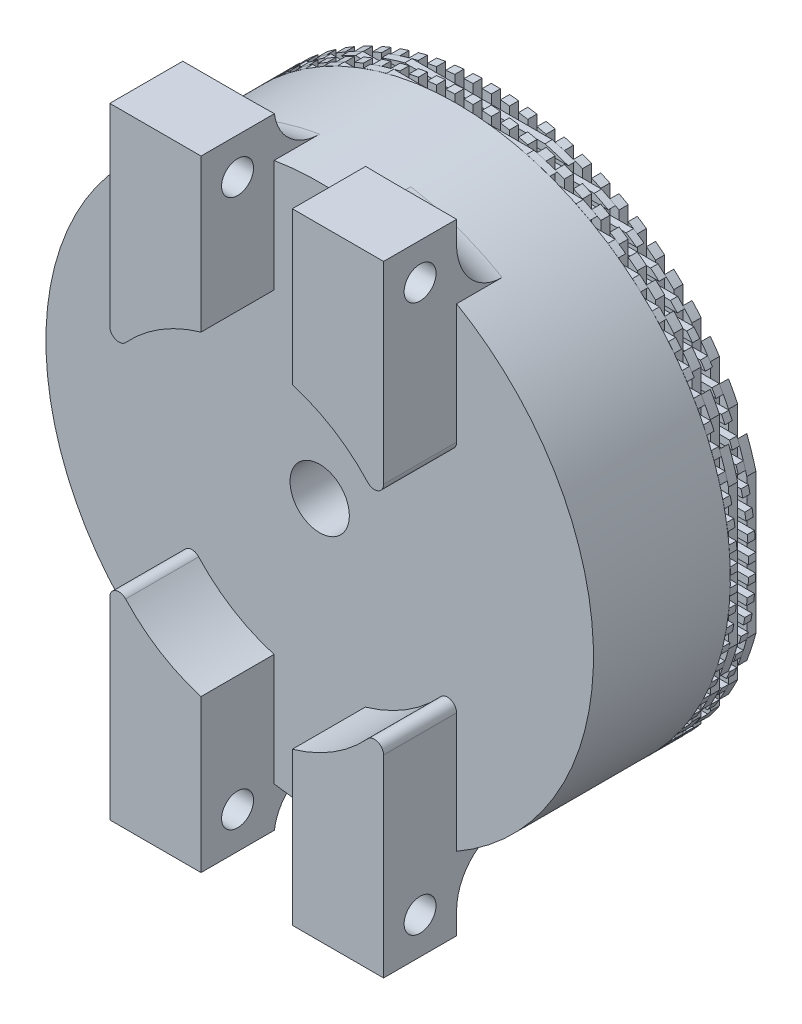
SolidWorks part; units mm, degrees
ref_plane "Front Plane" through (0, 0, 0) normal (1, 0, 0) x (0, 1, 0)
ref_plane "Top Plane" through (0, 0, 0) normal (0, 0, 1) x (0, 1, 0)
ref_plane "Right Plane" through (0, 0, 0) normal (0, 1, 0) x (-1, 0, 0)
sketch "Sketch1" plane through (0, 0, 0) normal (1, 0, 0) x (0, 1, 0)
  line L0 (64, -4) -> (68, -4) construction
  line L1 (0, 0) -> (68, 0)
  line L2 (0, 0) -> (0, -8)
  line L3 (0, -8) -> (68, -8)
  line L4 (68, 0) -> (68, -8)
  line L5 (4, -4) -> (0, -4) construction
  circle A0 centre (4, -4) radius 1.75
  circle A1 centre (64, -4) radius 1.75
  point P10 (0, -4)
  dimension "D1" = 3.5
  dimension "D2" = 60
  dimension "D3" = 8
  dimension "D4" = 4
extrude "Boss-Extrude1" add sketch "Sketch1" along normal blind 30
sketch "Sketch3" plane through (0, 0, -8) normal (0, 0, -1) x (1, 0, 0)
  line L1 (30, 0) -> (30, -68) construction
  line L2 (15, -34) -> (30, -34) construction
  line L3 (15, -34) -> (0, -34) construction
  line L4 (0, 0) -> (0, -68) construction
  circle A0 centre (15, -34) radius 30
  dimension "D1" = 60
extrude "Boss-Extrude2" add sketch "Sketch3" along normal blind 15
sketch "Sketch4" plane through (0, 0, 0) normal (0, 0, 1) x (1, 0, 0)
  circle A0 centre (15, 34) radius 18
  dimension "D1" = 36
extrude "Cut-Extrude1" cut sketch "Sketch4" against normal up to surface (8 mm away) and the other way through all up to face at (37.5, 34, -8)
ref_plane "Plane1" through (15, 0, 0) normal (1, 0, 0) x (0, 0, -1)
sketch "Sketch5" plane through (15, 0, 0) normal (1, 0, 0) x (0, 0, -1)
  line L0 (23, 4) -> (23, 64) construction
  line L1 (23, 63) -> (23.8, 63)
  line L2 (23, 63) -> (23, 62.2)
  line L3 (23, 62.2) -> (23.8, 62.2)
  line L4 (23.8, 63) -> (23.8, 62.2)
  line L5 (23, 64) -> (8, 64) construction
  line L6 (23, 61) -> (23, 60.2)
  line L7 (23, 61) -> (23.8, 61)
  line L8 (23.8, 61) -> (23.8, 60.2)
  line L9 (23, 60.2) -> (23.8, 60.2)
  line L10 (23, 59) -> (23, 58.2)
  line L11 (23, 59) -> (23.8, 59)
  line L12 (23.8, 59) -> (23.8, 58.2)
  line L13 (23, 58.2) -> (23.8, 58.2)
  line L14 (23, 57) -> (23, 56.2)
  line L15 (23, 57) -> (23.8, 57)
  line L16 (23.8, 57) -> (23.8, 56.2)
  line L17 (23, 56.2) -> (23.8, 56.2)
  line L18 (23, 55) -> (23, 54.2)
  line L19 (23, 55) -> (23.8, 55)
  line L20 (23.8, 55) -> (23.8, 54.2)
  line L21 (23, 54.2) -> (23.8, 54.2)
  line L22 (23, 53) -> (23, 52.2)
  line L23 (23, 53) -> (23.8, 53)
  line L24 (23.8, 53) -> (23.8, 52.2)
  line L25 (23, 52.2) -> (23.8, 52.2)
  line L26 (23, 51) -> (23, 50.2)
  line L27 (23, 51) -> (23.8, 51)
  line L28 (23.8, 51) -> (23.8, 50.2)
  line L29 (23, 50.2) -> (23.8, 50.2)
  line L30 (23, 49) -> (23, 48.2)
  line L31 (23, 49) -> (23.8, 49)
  line L32 (23.8, 49) -> (23.8, 48.2)
  line L33 (23, 48.2) -> (23.8, 48.2)
  line L34 (23, 47) -> (23, 46.2)
  line L35 (23, 47) -> (23.8, 47)
  line L36 (23.8, 47) -> (23.8, 46.2)
  line L37 (23, 46.2) -> (23.8, 46.2)
  line L38 (23, 45) -> (23, 44.2)
  line L39 (23, 45) -> (23.8, 45)
  line L40 (23.8, 45) -> (23.8, 44.2)
  line L41 (23, 44.2) -> (23.8, 44.2)
  line L42 (23, 43) -> (23, 42.2)
  line L43 (23, 43) -> (23.8, 43)
  line L44 (23.8, 43) -> (23.8, 42.2)
  line L45 (23, 42.2) -> (23.8, 42.2)
  line L46 (23, 41) -> (23, 40.2)
  line L47 (23, 41) -> (23.8, 41)
  line L48 (23.8, 41) -> (23.8, 40.2)
  line L49 (23, 40.2) -> (23.8, 40.2)
  line L50 (23, 39) -> (23, 38.2)
  line L51 (23, 39) -> (23.8, 39)
  line L52 (23.8, 39) -> (23.8, 38.2)
  line L53 (23, 38.2) -> (23.8, 38.2)
  line L54 (23, 37) -> (23, 36.2)
  line L55 (23, 37) -> (23.8, 37)
  line L56 (23.8, 37) -> (23.8, 36.2)
  line L57 (23, 36.2) -> (23.8, 36.2)
  line L58 (23, 35) -> (23, 34.2)
  line L59 (23, 35) -> (23.8, 35)
  line L60 (23.8, 35) -> (23.8, 34.2)
  line L61 (23, 34.2) -> (23.8, 34.2)
  line L62 (23, 33) -> (23, 32.2)
  line L63 (23, 33) -> (23.8, 33)
  line L64 (23.8, 33) -> (23.8, 32.2)
  line L65 (23, 32.2) -> (23.8, 32.2)
  line L66 (23, 31) -> (23, 30.2)
  line L67 (23, 31) -> (23.8, 31)
  line L68 (23.8, 31) -> (23.8, 30.2)
  line L69 (23, 30.2) -> (23.8, 30.2)
  line L70 (23, 29) -> (23, 28.2)
  line L71 (23, 29) -> (23.8, 29)
  line L72 (23.8, 29) -> (23.8, 28.2)
  line L73 (23, 28.2) -> (23.8, 28.2)
  line L74 (23, 27) -> (23, 26.2)
  line L75 (23, 27) -> (23.8, 27)
  line L76 (23.8, 27) -> (23.8, 26.2)
  line L77 (23, 26.2) -> (23.8, 26.2)
  line L78 (23, 25) -> (23, 24.2)
  line L79 (23, 25) -> (23.8, 25)
  line L80 (23.8, 25) -> (23.8, 24.2)
  line L81 (23, 24.2) -> (23.8, 24.2)
  line L82 (23, 23) -> (23, 22.2)
  line L83 (23, 23) -> (23.8, 23)
  line L84 (23.8, 23) -> (23.8, 22.2)
  line L85 (23, 22.2) -> (23.8, 22.2)
  line L86 (23, 21) -> (23, 20.2)
  line L87 (23, 21) -> (23.8, 21)
  line L88 (23.8, 21) -> (23.8, 20.2)
  line L89 (23, 20.2) -> (23.8, 20.2)
  line L90 (23, 19) -> (23, 18.2)
  line L91 (23, 19) -> (23.8, 19)
  line L92 (23.8, 19) -> (23.8, 18.2)
  line L93 (23, 18.2) -> (23.8, 18.2)
  line L94 (23, 17) -> (23, 16.2)
  line L95 (23, 17) -> (23.8, 17)
  line L96 (23.8, 17) -> (23.8, 16.2)
  line L97 (23, 16.2) -> (23.8, 16.2)
  line L98 (23, 15) -> (23, 14.2)
  line L99 (23, 15) -> (23.8, 15)
  line L100 (23.8, 15) -> (23.8, 14.2)
  line L101 (23, 14.2) -> (23.8, 14.2)
  line L102 (23, 13) -> (23, 12.2)
  line L103 (23, 13) -> (23.8, 13)
  line L104 (23.8, 13) -> (23.8, 12.2)
  line L105 (23, 12.2) -> (23.8, 12.2)
  line L106 (23, 11) -> (23, 10.2)
  line L107 (23, 11) -> (23.8, 11)
  line L108 (23.8, 11) -> (23.8, 10.2)
  line L109 (23, 10.2) -> (23.8, 10.2)
  line L110 (23, 9) -> (23, 8.2)
  line L111 (23, 9) -> (23.8, 9)
  line L112 (23.8, 9) -> (23.8, 8.2)
  line L113 (23, 8.2) -> (23.8, 8.2)
  line L114 (23, 7) -> (23, 6.2)
  line L115 (23, 7) -> (23.8, 7)
  line L116 (23.8, 7) -> (23.8, 6.2)
  line L117 (23, 6.2) -> (23.8, 6.2)
  line L118 (23, 5) -> (23, 4.2)
  line L119 (23, 5) -> (23.8, 5)
  line L120 (23.8, 5) -> (23.8, 4.2)
  line L121 (23, 4.2) -> (23.8, 4.2)
  line L122 (23, 3) -> (23, 2.2)
  line L123 (23, 3) -> (23.8, 3)
  line L124 (23.8, 3) -> (23.8, 2.2)
  line L125 (23, 2.2) -> (23.8, 2.2)
  line L126 (23, 63) -> (23, 61) construction
  dimension "D1" = 0.8
  dimension "D2" = 1
  dimension "D4" = 2
  dimension "D3" = 31
extrude "Boss-Extrude3" add sketch "Sketch5" along normal mid plane 75 separate body
ref_plane "Plane2" through (0, 34, 0) normal (0, -1, 0) x (-1, 0, 0)
sketch "Sketch6" plane through (0, 34, 0) normal (0, -1, 0) x (-1, 0, 0)
  line L0 (-52.5, 23.8) -> (22.5, 23.8) construction
  line L1 (-44, 23.8) -> (-43, 23.8)
  line L2 (-44, 23.8) -> (-44, 24.8)
  line L3 (-44, 24.8) -> (-43, 24.8)
  line L4 (-43, 23.8) -> (-43, 24.8)
  line L5 (-45, 23) -> (-45, 8) construction
  line L6 (-42, 23.8) -> (-42, 24.8)
  line L7 (-42, 23.8) -> (-41, 23.8)
  line L8 (-41, 23.8) -> (-41, 24.8)
  line L9 (-42, 24.8) -> (-41, 24.8)
  line L10 (-40, 23.8) -> (-40, 24.8)
  line L11 (-40, 23.8) -> (-39, 23.8)
  line L12 (-39, 23.8) -> (-39, 24.8)
  line L13 (-40, 24.8) -> (-39, 24.8)
  line L14 (-38, 23.8) -> (-38, 24.8)
  line L15 (-38, 23.8) -> (-37, 23.8)
  line L16 (-37, 23.8) -> (-37, 24.8)
  line L17 (-38, 24.8) -> (-37, 24.8)
  line L18 (-36, 23.8) -> (-36, 24.8)
  line L19 (-36, 23.8) -> (-35, 23.8)
  line L20 (-35, 23.8) -> (-35, 24.8)
  line L21 (-36, 24.8) -> (-35, 24.8)
  line L22 (-34, 23.8) -> (-34, 24.8)
  line L23 (-34, 23.8) -> (-33, 23.8)
  line L24 (-33, 23.8) -> (-33, 24.8)
  line L25 (-34, 24.8) -> (-33, 24.8)
  line L26 (-32, 23.8) -> (-32, 24.8)
  line L27 (-32, 23.8) -> (-31, 23.8)
  line L28 (-31, 23.8) -> (-31, 24.8)
  line L29 (-32, 24.8) -> (-31, 24.8)
  line L30 (-30, 23.8) -> (-30, 24.8)
  line L31 (-30, 23.8) -> (-29, 23.8)
  line L32 (-29, 23.8) -> (-29, 24.8)
  line L33 (-30, 24.8) -> (-29, 24.8)
  line L34 (-28, 23.8) -> (-28, 24.8)
  line L35 (-28, 23.8) -> (-27, 23.8)
  line L36 (-27, 23.8) -> (-27, 24.8)
  line L37 (-28, 24.8) -> (-27, 24.8)
  line L38 (-26, 23.8) -> (-26, 24.8)
  line L39 (-26, 23.8) -> (-25, 23.8)
  line L40 (-25, 23.8) -> (-25, 24.8)
  line L41 (-26, 24.8) -> (-25, 24.8)
  line L42 (-24, 23.8) -> (-24, 24.8)
  line L43 (-24, 23.8) -> (-23, 23.8)
  line L44 (-23, 23.8) -> (-23, 24.8)
  line L45 (-24, 24.8) -> (-23, 24.8)
  line L46 (-22, 23.8) -> (-22, 24.8)
  line L47 (-22, 23.8) -> (-21, 23.8)
  line L48 (-21, 23.8) -> (-21, 24.8)
  line L49 (-22, 24.8) -> (-21, 24.8)
  line L50 (-20, 23.8) -> (-20, 24.8)
  line L51 (-20, 23.8) -> (-19, 23.8)
  line L52 (-19, 23.8) -> (-19, 24.8)
  line L53 (-20, 24.8) -> (-19, 24.8)
  line L54 (-18, 23.8) -> (-18, 24.8)
  line L55 (-18, 23.8) -> (-17, 23.8)
  line L56 (-17, 23.8) -> (-17, 24.8)
  line L57 (-18, 24.8) -> (-17, 24.8)
  line L58 (-16, 23.8) -> (-16, 24.8)
  line L59 (-16, 23.8) -> (-15, 23.8)
  line L60 (-15, 23.8) -> (-15, 24.8)
  line L61 (-16, 24.8) -> (-15, 24.8)
  line L62 (-14, 23.8) -> (-14, 24.8)
  line L63 (-14, 23.8) -> (-13, 23.8)
  line L64 (-13, 23.8) -> (-13, 24.8)
  line L65 (-14, 24.8) -> (-13, 24.8)
  line L66 (-12, 23.8) -> (-12, 24.8)
  line L67 (-12, 23.8) -> (-11, 23.8)
  line L68 (-11, 23.8) -> (-11, 24.8)
  line L69 (-12, 24.8) -> (-11, 24.8)
  line L70 (-10, 23.8) -> (-10, 24.8)
  line L71 (-10, 23.8) -> (-9, 23.8)
  line L72 (-9, 23.8) -> (-9, 24.8)
  line L73 (-10, 24.8) -> (-9, 24.8)
  line L74 (-8, 23.8) -> (-8, 24.8)
  line L75 (-8, 23.8) -> (-7, 23.8)
  line L76 (-7, 23.8) -> (-7, 24.8)
  line L77 (-8, 24.8) -> (-7, 24.8)
  line L78 (-6, 23.8) -> (-6, 24.8)
  line L79 (-6, 23.8) -> (-5, 23.8)
  line L80 (-5, 23.8) -> (-5, 24.8)
  line L81 (-6, 24.8) -> (-5, 24.8)
  line L82 (-4, 23.8) -> (-4, 24.8)
  line L83 (-4, 23.8) -> (-3, 23.8)
  line L84 (-3, 23.8) -> (-3, 24.8)
  line L85 (-4, 24.8) -> (-3, 24.8)
  line L86 (-2, 23.8) -> (-2, 24.8)
  line L87 (-2, 23.8) -> (-1, 23.8)
  line L88 (-1, 23.8) -> (-1, 24.8)
  line L89 (-2, 24.8) -> (-1, 24.8)
  line L90 (0, 23.8) -> (0, 24.8)
  line L91 (0, 23.8) -> (1, 23.8)
  line L92 (1, 23.8) -> (1, 24.8)
  line L93 (0, 24.8) -> (1, 24.8)
  line L94 (2, 23.8) -> (2, 24.8)
  line L95 (2, 23.8) -> (3, 23.8)
  line L96 (3, 23.8) -> (3, 24.8)
  line L97 (2, 24.8) -> (3, 24.8)
  line L98 (4, 23.8) -> (4, 24.8)
  line L99 (4, 23.8) -> (5, 23.8)
  line L100 (5, 23.8) -> (5, 24.8)
  line L101 (4, 24.8) -> (5, 24.8)
  line L102 (6, 23.8) -> (6, 24.8)
  line L103 (6, 23.8) -> (7, 23.8)
  line L104 (7, 23.8) -> (7, 24.8)
  line L105 (6, 24.8) -> (7, 24.8)
  line L106 (8, 23.8) -> (8, 24.8)
  line L107 (8, 23.8) -> (9, 23.8)
  line L108 (9, 23.8) -> (9, 24.8)
  line L109 (8, 24.8) -> (9, 24.8)
  line L110 (10, 23.8) -> (10, 24.8)
  line L111 (10, 23.8) -> (11, 23.8)
  line L112 (11, 23.8) -> (11, 24.8)
  line L113 (10, 24.8) -> (11, 24.8)
  line L114 (12, 23.8) -> (12, 24.8)
  line L115 (12, 23.8) -> (13, 23.8)
  line L116 (13, 23.8) -> (13, 24.8)
  line L117 (12, 24.8) -> (13, 24.8)
  line L118 (14, 23.8) -> (14, 24.8)
  line L119 (14, 23.8) -> (15, 23.8)
  line L120 (15, 23.8) -> (15, 24.8)
  line L121 (14, 24.8) -> (15, 24.8)
  line L122 (16, 23.8) -> (16, 24.8)
  line L123 (16, 23.8) -> (17, 23.8)
  line L124 (17, 23.8) -> (17, 24.8)
  line L125 (16, 24.8) -> (17, 24.8)
  line L126 (-44, 23.8) -> (-42, 23.8) construction
  dimension "D1" = 1
  dimension "D2" = 1
  dimension "D4" = 2
  dimension "D3" = 31
extrude "Boss-Extrude4" add sketch "Sketch6" along normal mid plane 74 separate body
pattern_linear "LPattern1" count 2 spacing 2 along (0, 0, -1) of "Boss-Extrude3", "Boss-Extrude4"
sketch "Sketch7" plane through (0, 0, -8) normal (0, 0, -1) x (1, 0, 0)
  circle A0 centre (15, -34) radius 30
  circle A4 centre (15, -34) radius 30 construction
  circle A5 centre (15, -34) radius 72.5485
  dimension "D1" = 60
extrude "Cut-Extrude2" cut sketch "Sketch7" along normal through all contours A5 A0 region at (-55.4965, 34, -8)
fillet "Fillet3" radius 1 4 edges at (30, 24.0501, -4) (30, 43.9499, -4) (0, 43.9499, -4) (0, 24.0501, -4)
sketch "Sketch8" plane through (0, 0, 0) normal (0, 0, 1) x (1, 0, 0)
  line L0 (20, 34) -> (15, 34) construction
  line L1 (10, 71.5) -> (20, 71.5)
  line L2 (10, 71.5) -> (10, -3.5)
  line L3 (10, -3.5) -> (20, -3.5)
  line L4 (20, 71.5) -> (20, -3.5)
  line L5 (15, -13.3161) -> (15, 13.3161) construction
  line L6 (15, 34) -> (10, 34) construction
  line L7 (-10.9219, 34) -> (10.9219, 34) construction
  dimension "D1" = 10
  dimension "D2" = 75
extrude "Cut-Extrude3" cut sketch "Sketch8" against normal up to surface (8 mm away) up to face at (15, 34, -8)
fillet "Fillet1" radius 5 4 edges at (25.1607, 5.7731, -8) (4.8393, 5.7731, -8) (4.8393, 62.2269, -8) (25.1607, 62.2269, -8)
sketch "Sketch9" plane through (0, 0, -8) normal (0, 0, 1) x (1, 0, 0)
  circle A0 centre (15, 34) radius 3.25
  dimension "D1" = 6.5
extrude "Cut-Extrude4" cut sketch "Sketch9" against normal up to surface (15 mm away) up to face at (15, 64, -23)
sketch "Sketch10" plane through (0, 0, -23) normal (0, 0, -1) x (-1, 0, 0)
  line L0 (-15, 34) -> (-45, 34) construction
  circle A0 centre (-23, 34) radius 1.25
  circle A1 centre (-19, 40.9282) radius 1.25
  circle A2 centre (-15, 34) radius 8 construction
  circle A3 centre (-15, 34) radius 3.25 construction
  circle A4 centre (-15, 34) radius 30 construction
  circle A5 centre (-27, 34) radius 1.25
  circle A6 centre (-32, 34) radius 1.25
  circle A7 centre (-38, 34) radius 1.25
  circle A8 centre (-21, 44.3923) radius 1.25
  circle A9 centre (-23.5, 48.7224) radius 1.25
  circle A10 centre (-26.5, 53.9186) radius 1.25
  circle A11 centre (-11, 40.9282) radius 1.25
  circle A12 centre (-9, 44.3923) radius 1.25
  circle A13 centre (-6.5, 48.7224) radius 1.25
  circle A14 centre (-3.5, 53.9186) radius 1.25
  circle A15 centre (-7, 34) radius 1.25
  circle A16 centre (-3, 34) radius 1.25
  circle A17 centre (2, 34) radius 1.25
  circle A18 centre (8, 34) radius 1.25
  circle A19 centre (-11, 27.0718) radius 1.25
  circle A20 centre (-9, 23.6077) radius 1.25
  circle A21 centre (-6.5, 19.2776) radius 1.25
  circle A22 centre (-3.5, 14.0814) radius 1.25
  circle A23 centre (-19, 27.0718) radius 1.25
  circle A24 centre (-21, 23.6077) radius 1.25
  circle A25 centre (-23.5, 19.2776) radius 1.25
  circle A26 centre (-26.5, 14.0814) radius 1.25
  dimension "D1" = 2.5
  dimension "D2" = 16
  dimension "D3" = 4
  dimension "D4" = 5
  dimension "D5" = 6
  dimension "D6" = 6
extrude "Cut-Extrude5" cut sketch "Sketch10" against normal blind 8 draft 5 draft outward yes
